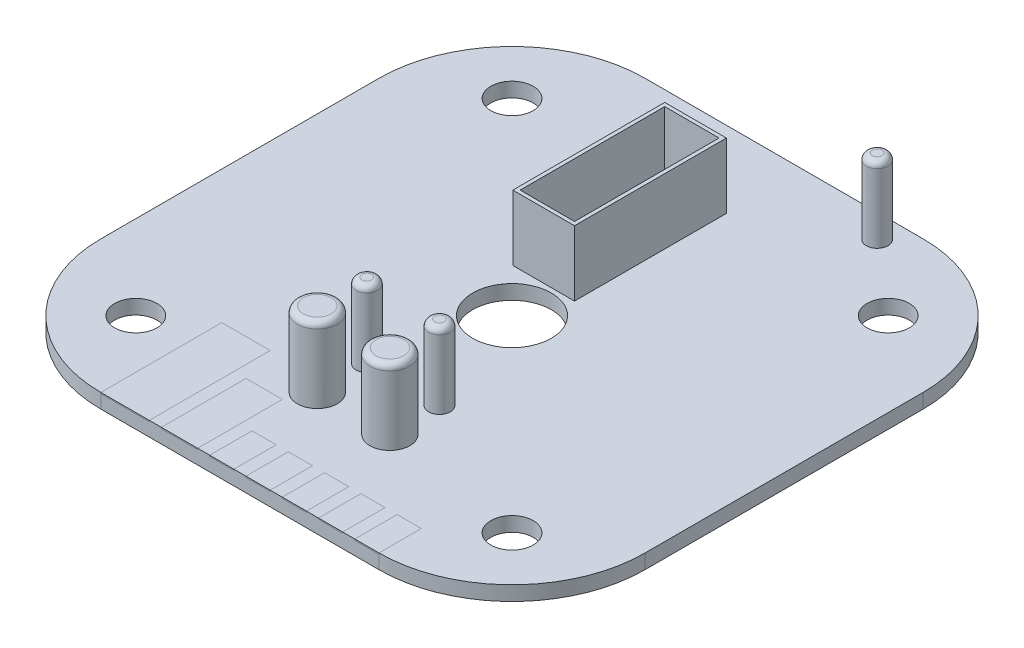
SolidWorks part; units mm, degrees
ref_plane "Front Plane" through (0, 0, 0) normal (0, 0, 1) x (1, 0, 0)
ref_plane "Top Plane" through (0, 0, 0) normal (0, 1, 0) x (1, 0, 0)
ref_plane "Right Plane" through (0, 0, 0) normal (1, 0, 0) x (0, 0, -1)
sketch "Sketch1" plane through (0, 0, 0) normal (0, 1, 0) x (1, 0, 0)
  line L1 (-22.5, -22.5) -> (22.5, -22.5)
  line L2 (-22.5, -22.5) -> (-22.5, 22.5)
  line L3 (-22.5, 22.5) -> (22.5, 22.5)
  line L4 (22.5, -22.5) -> (22.5, 22.5)
  line L5 (-22.5, -22.5) -> (22.5, 22.5) construction
  line L6 (-22.5, 22.5) -> (22.5, -22.5) construction
  point P0 (0, 0)
  dimension "D1" = 45
extrude "Boss-Extrude1" add sketch "Sketch1" along normal mid plane 1.2
sketch "Sketch3" plane through (0, 0, 0) normal (0, 1, 0) x (1, 0, 0)
  circle A0 centre (0, 0) radius 3.25
  dimension "D1" = 6.5
extrude "Cut-Extrude1" cut sketch "Sketch3" against normal through all both and the other way through all
fillet "Fillet1" radius 11 4 edges at (22.5, 0, 22.5) (-22.5, 0, 22.5) (-22.5, 0, -22.5) (22.5, 0, -22.5)
sketch "Sketch5" plane through (0, 0, 0) normal (0, 1, 0) x (1, 0, 0)
  line L0 (-15.5563, -15.5563) -> (15.5563, 15.5563) construction
  line L1 (-15.5563, 15.5563) -> (15.5563, -15.5563) construction
  line L2 (0, 0) -> (0, 22) construction
  circle A0 centre (0, 0) radius 22 construction
  circle A1 centre (-15.5563, 15.5563) radius 1.75
  circle A2 centre (15.5563, 15.5563) radius 1.75
  circle A3 centre (15.5563, -15.5563) radius 1.75
  circle A4 centre (-15.5563, -15.5563) radius 1.75
  point P6 (0, 0)
  point P9 (0, 0)
  dimension "D2" = 3.5
  dimension "D3" = 44
  dimension "D1" = 45
extrude "Cut-Extrude2" cut sketch "Sketch5" against normal through all both and the other way through all
sketch "Sketch6" plane through (0, 0.6, 0) normal (0, 1, 0) x (1, 0, 0)
  line L1 (-3.5563, 3.6263) -> (1.5437, 3.6263)
  line L2 (-3.5563, 3.6263) -> (-3.5563, 16.1863)
  line L3 (-3.5563, 16.1863) -> (1.5437, 16.1863)
  line L4 (1.5437, 3.6263) -> (1.5437, 16.1863)
  line L5 (-3.5563, 3.6263) -> (1.5437, 16.1863) construction
  line L6 (-3.5563, 16.1863) -> (1.5437, 3.6263) construction
  circle A0 centre (-15.5563, 15.5563) radius 1.75 construction
  circle A1 centre (15.5563, 15.5563) radius 1.75 construction
  point P0 (-1.0063, 9.9063)
  dimension "D3" = 14.55
  dimension "D4" = 5.65
  dimension "D1" = 5.1
  dimension "D2" = 12.56
extrude "Extrude-Thin1" add sketch "Sketch6" along normal blind 5.4 thin thin type one direction reverse wall 0.3
sketch "Sketch7" plane through (0, 0.6, 0) normal (0, 1, 0) x (1, 0, 0)
  line L0 (1.2437, 3.9263) -> (1.2437, 15.8863) construction
  line L1 (-3.2563, 3.9263) -> (1.2437, 3.9263) construction
  line L2 (-3.2563, 15.8863) -> (-3.2563, 3.9263) construction
  line L3 (1.2437, 15.8863) -> (-3.2563, 15.8863) construction
  line L4 (1.2437, 3.9263) -> (1.2437, 15.8863)
  line L5 (-3.2563, 3.9263) -> (1.2437, 3.9263)
  line L6 (-3.2563, 15.8863) -> (-3.2563, 3.9263)
  line L7 (1.2437, 15.8863) -> (-3.2563, 15.8863)
extrude "Boss-Extrude2" add sketch "Sketch7" along normal blind 0.3
sketch "Sketch8" plane through (0, 0.6, 0) normal (0, 1, 0) x (1, 0, 0)
  line L0 (-11.5, -22.5) -> (11.5, -22.5) construction
  line L1 (-2.5, -22.5) -> (-0.5, -22.5)
  line L2 (-2.5, -22.5) -> (-2.5, -19)
  line L3 (-2.5, -19) -> (-0.5, -19)
  line L4 (-0.5, -22.5) -> (-0.5, -19)
  line L5 (-0.5, -19) -> (0.5, -19) construction
  line L6 (0.5, -22.5) -> (2.5, -22.5)
  line L7 (0.5, -22.5) -> (0.5, -19)
  line L8 (0.5, -19) -> (2.5, -19)
  line L9 (2.5, -22.5) -> (2.5, -19)
  line L10 (3.5, -22.5) -> (5.5, -22.5)
  line L11 (3.5, -22.5) -> (3.5, -19)
  line L12 (3.5, -19) -> (5.5, -19)
  line L13 (5.5, -22.5) -> (5.5, -19)
  line L14 (6.5, -22.5) -> (8.5, -22.5)
  line L15 (6.5, -22.5) -> (6.5, -19)
  line L16 (6.5, -19) -> (8.5, -19)
  line L17 (8.5, -22.5) -> (8.5, -19)
  line L18 (9.5, -22.5) -> (11.5, -22.5)
  line L19 (9.5, -22.5) -> (9.5, -19)
  line L20 (9.5, -19) -> (11.5, -19)
  line L21 (11.5, -22.5) -> (11.5, -19)
  line L22 (2.5, -19) -> (3.5, -19) construction
  line L23 (5.5, -19) -> (6.5, -19) construction
  line L24 (8.5, -19) -> (9.5, -19) construction
  line L26 (-11.5, -22.5) -> (-7.5, -22.5)
  line L27 (-11.5, -22.5) -> (-11.5, -12.5)
  line L28 (-11.5, -12.5) -> (-7.5, -12.5)
  line L29 (-7.5, -22.5) -> (-7.5, -12.5)
  line L30 (-6.5, -22.5) -> (-3.5, -22.5)
  line L31 (-6.5, -22.5) -> (-6.5, -15.5)
  line L32 (-6.5, -15.5) -> (-3.5, -15.5)
  line L33 (-3.5, -22.5) -> (-3.5, -15.5)
  dimension "D1" = 2
  dimension "D2" = 1
  dimension "D3" = 3.5
  dimension "D4" = 10
  dimension "D5" = 4
  dimension "D6" = 1
  dimension "D7" = 3
  dimension "D8" = 7
  dimension "D9" = 1
extrude "Cut-Extrude3" cut sketch "Sketch8" against normal blind 0.1
sketch "Sketch9" plane through (0, 0.5, 0) normal (0, 1, 0) x (1, 0, 0)
  line L0 (9.5, -19) -> (9.5, -22.5) construction
  line L1 (9.5, -22.5) -> (11.5, -22.5) construction
  line L2 (11.5, -22.5) -> (11.5, -19) construction
  line L3 (11.5, -19) -> (9.5, -19) construction
  line L4 (6.5, -19) -> (6.5, -22.5) construction
  line L5 (6.5, -22.5) -> (8.5, -22.5) construction
  line L6 (8.5, -22.5) -> (8.5, -19) construction
  line L7 (8.5, -19) -> (6.5, -19) construction
  line L8 (3.5, -19) -> (3.5, -22.5) construction
  line L9 (3.5, -22.5) -> (5.5, -22.5) construction
  line L10 (5.5, -22.5) -> (5.5, -19) construction
  line L11 (5.5, -19) -> (3.5, -19) construction
  line L12 (0.5, -19) -> (0.5, -22.5) construction
  line L13 (0.5, -22.5) -> (2.5, -22.5) construction
  line L14 (2.5, -22.5) -> (2.5, -19) construction
  line L15 (2.5, -19) -> (0.5, -19) construction
  line L16 (-2.5, -19) -> (-2.5, -22.5) construction
  line L17 (-2.5, -22.5) -> (-0.5, -22.5) construction
  line L18 (-0.5, -22.5) -> (-0.5, -19) construction
  line L19 (-0.5, -19) -> (-2.5, -19) construction
  line L20 (-6.5, -15.5) -> (-6.5, -22.5) construction
  line L21 (-6.5, -22.5) -> (-3.5, -22.5) construction
  line L22 (-3.5, -22.5) -> (-3.5, -15.5) construction
  line L23 (-3.5, -15.5) -> (-6.5, -15.5) construction
  line L24 (-11.5, -12.5) -> (-11.5, -22.5) construction
  line L25 (-11.5, -22.5) -> (-7.5, -22.5) construction
  line L26 (-7.5, -22.5) -> (-7.5, -12.5) construction
  line L27 (-7.5, -12.5) -> (-11.5, -12.5) construction
  line L28 (9.5, -19) -> (9.5, -22.5)
  line L29 (9.5, -22.5) -> (11.5, -22.5)
  line L30 (11.5, -22.5) -> (11.5, -19)
  line L31 (11.5, -19) -> (9.5, -19)
  line L32 (6.5, -19) -> (6.5, -22.5)
  line L33 (6.5, -22.5) -> (8.5, -22.5)
  line L34 (8.5, -22.5) -> (8.5, -19)
  line L35 (8.5, -19) -> (6.5, -19)
  line L36 (3.5, -19) -> (3.5, -22.5)
  line L37 (3.5, -22.5) -> (5.5, -22.5)
  line L38 (5.5, -22.5) -> (5.5, -19)
  line L39 (5.5, -19) -> (3.5, -19)
  line L40 (0.5, -19) -> (0.5, -22.5)
  line L41 (0.5, -22.5) -> (2.5, -22.5)
  line L42 (2.5, -22.5) -> (2.5, -19)
  line L43 (2.5, -19) -> (0.5, -19)
  line L44 (-2.5, -19) -> (-2.5, -22.5)
  line L45 (-2.5, -22.5) -> (-0.5, -22.5)
  line L46 (-0.5, -22.5) -> (-0.5, -19)
  line L47 (-0.5, -19) -> (-2.5, -19)
  line L48 (-6.5, -15.5) -> (-6.5, -22.5)
  line L49 (-6.5, -22.5) -> (-3.5, -22.5)
  line L50 (-3.5, -22.5) -> (-3.5, -15.5)
  line L51 (-3.5, -15.5) -> (-6.5, -15.5)
  line L52 (-11.5, -12.5) -> (-11.5, -22.5)
  line L53 (-11.5, -22.5) -> (-7.5, -22.5)
  line L54 (-7.5, -22.5) -> (-7.5, -12.5)
  line L55 (-7.5, -12.5) -> (-11.5, -12.5)
extrude "Boss-Extrude3" add sketch "Sketch9" along normal up to surface (0.1 mm away) separate body up to face at (-15.5563, 0.6, 17.3063)
sketch "Sketch10" plane through (0, 0.6, 0) normal (0, 1, 0) x (1, 0, 0)
  line L0 (-2.5563, -9.4437) -> (-2.5563, -13.5437) construction
  line L1 (3.4437, -9.4437) -> (3.4437, -13.5437) construction
  line L2 (-2.5563, -11.4937) -> (3.4437, -11.4937) construction
  circle A0 centre (3.4437, -9.4437) radius 0.9
  circle A1 centre (3.4437, -13.5437) radius 1.65
  circle A2 centre (-2.5563, -13.5437) radius 1.65
  circle A3 centre (-2.5563, -9.4437) radius 0.9
  circle A4 centre (9.6437, 20.5563) radius 0.9
  circle A5 centre (-15.5563, 15.5563) radius 1.75 construction
  dimension "D1" = 1.8
  dimension "D2" = 3.3
  dimension "D3" = 19
  dimension "D4" = 25
  dimension "D5" = 29.1
  dimension "D6" = 25.2
  dimension "D7" = 13
  dimension "D8" = 5
extrude "Boss-Extrude4" add sketch "Sketch10" along normal blind 6.2
fillet "Fillet2" radius 0.5 5 edges at (3.4437, 6.8, 15.1937) (3.4437, 6.8, 10.3437) (-2.5563, 6.8, 10.3437) (-2.5563, 6.8, 15.1937) (9.6437, 6.8, -19.6563)
